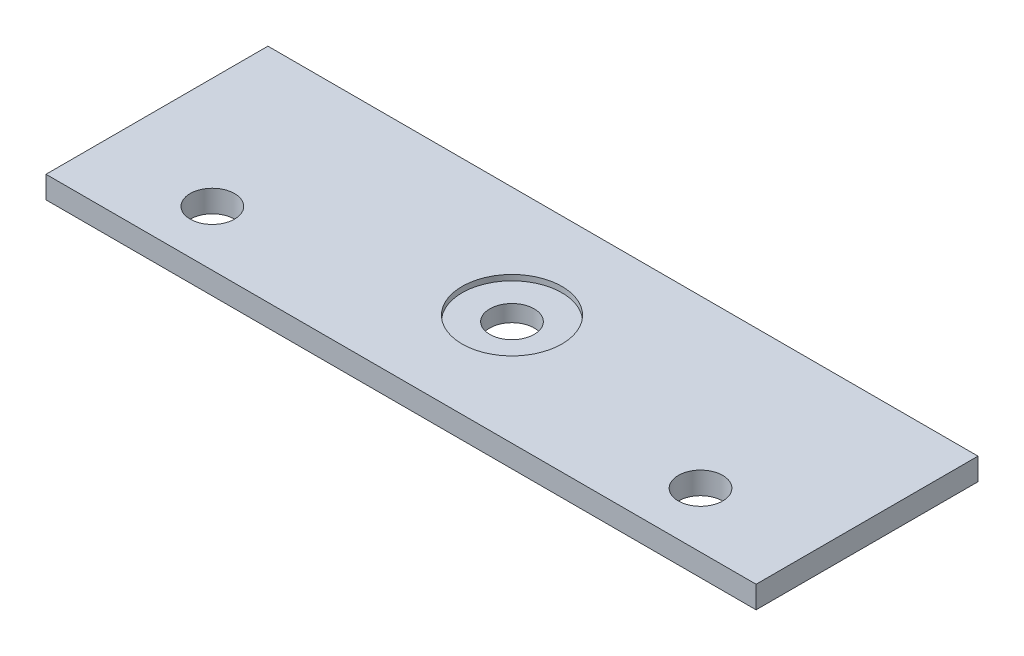
SolidWorks part; units mm, degrees
material "6061 Alloy"
ref_plane "Front" through (0, 0, 0) normal (0, 0, 1) x (1, 0, 0)
ref_plane "Top" through (0, 0, 0) normal (0, 1, 0) x (1, 0, 0)
ref_plane "Right" through (0, 0, 0) normal (1, 0, 0) x (0, 0, -1)
sketch "Sketch8" plane through (0, 0, 0) normal (0, 1, 0) x (1, 0, 0)
  line L0 (-101.6, 63.5) -> (-101.6, 0) construction
  line L1 (0, 0) -> (-203.2, 0)
  line L2 (0, 0) -> (0, 63.5)
  line L3 (0, 63.5) -> (-203.2, 63.5)
  line L4 (-203.2, 0) -> (-203.2, 63.5)
  dimension "D1" = 63.5
  dimension "D2" = 203.2
extrude "Boss-Extrude1" add sketch "Sketch8" along normal blind 6.35
sketch "Sketch9" plane through (0, 6.35, 0) normal (0, 1, 0) x (1, 0, 0)
  line L0 (-101.6, 63.5) -> (-101.6, 0) construction
  line L1 (0, 63.5) -> (-203.2, 63.5) construction
  line L2 (-203.2, 0) -> (0, 0) construction
  circle A0 centre (-101.6, 31.75) radius 14.2875
  dimension "D1" = 28.575
extrude "Cut-Extrude2" cut sketch "Sketch9" against normal blind 1.5875
sketch "Sketch10" plane through (0, 4.7625, 0) normal (0, 1, 0) x (1, 0, 0)
  circle A0 centre (-101.6, 31.75) radius 6.35
  dimension "D1" = 12.7
extrude "Cut-Extrude3" cut sketch "Sketch10" against normal through all
sketch "Sketch11" plane through (0, 6.35, 0) normal (0, 1, 0) x (1, 0, 0)
  line L0 (0, 63.5) -> (-203.2, 63.5) construction
  line L1 (-203.2, 63.5) -> (-203.2, 0) construction
  line L2 (0, 0) -> (0, 63.5) construction
  circle A0 centre (-171.45, 15.85) radius 6.35
  circle A1 centre (-31.75, 15.85) radius 6.35
  point P0 (-171.45, 24.6505)
  dimension "D1" = 12.7
  dimension "D3" = 12.7
  dimension "D2" = 31.75
  dimension "D4" = 31.75
  dimension "D5" = 47.65
extrude "Cut-Extrude4" cut sketch "Sketch11" against normal through all
